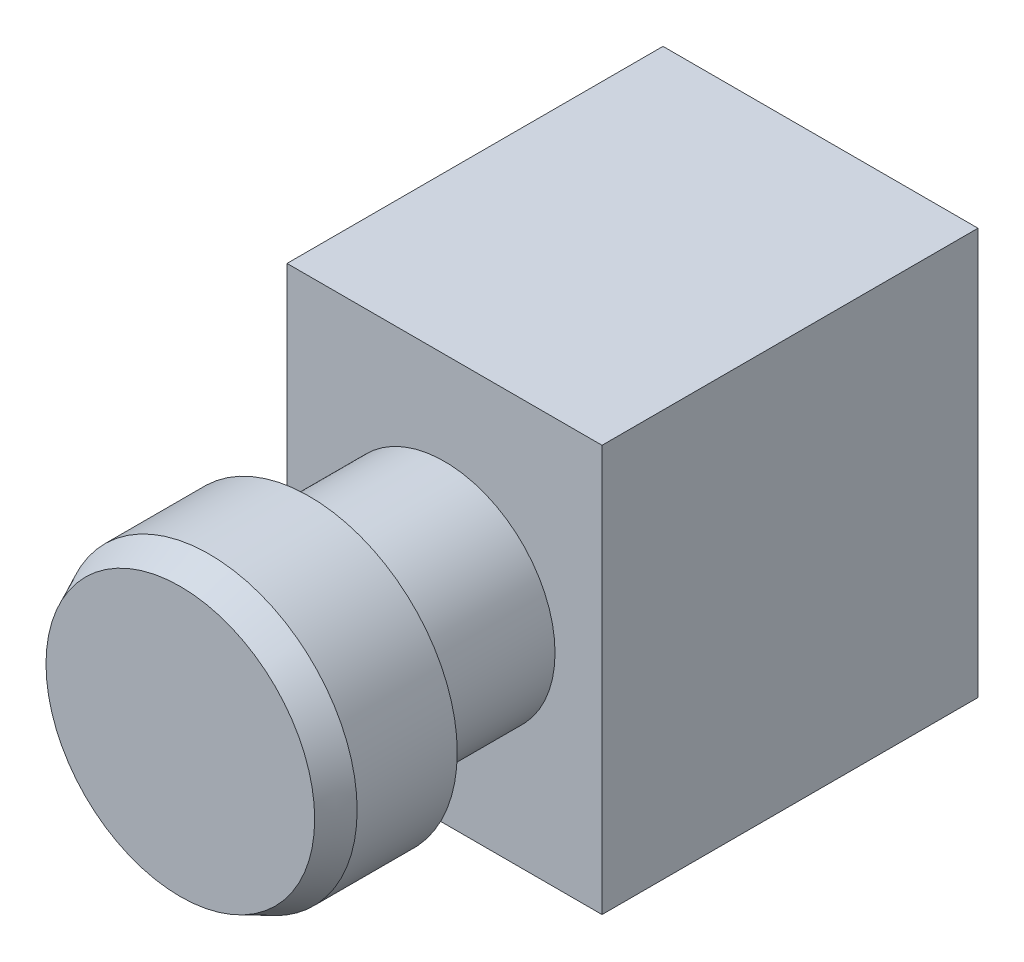
SolidWorks part; units mm, degrees
ref_plane "Front" through (0, 0, 0) normal (0, 0, 1) x (1, 0, 0)
ref_plane "Top" through (0, 0, 0) normal (0, 1, 0) x (1, 0, 0)
ref_plane "Right" through (0, 0, 0) normal (1, 0, 0) x (0, 0, -1)
sketch "Sketch1" plane through (0, 0, 0) normal (0, 0, 1) x (1, 0, 0)
  circle A0 centre (0, 0) radius 14.55
  dimension "D1" = 29.1
extrude "Boss-Extrude1" add sketch "Sketch1" along normal blind 9.85
sketch "Sketch3" plane through (0, 0, 9.85) normal (0, 0, 1) x (1, 0, 0)
  circle A1 centre (0, 0) radius 14.55
  circle A2 centre (0, 0) radius 14.55
  dimension "D1" = 0
extrude "Boss-Extrude3" add sketch "Sketch3" along normal blind 2.85 draft 25
sketch "Sketch4" plane through (0, 0, 0) normal (0, 0, 1) x (1, 0, 0)
  circle A0 centre (0, 0) radius 10.875
  point P2 (0, 0)
  dimension "D1" = 21.75
extrude "Boss-Extrude4" add sketch "Sketch4" against normal blind 13.3
sketch "Sketch2" plane through (0, 0, -13.3) normal (0, 0, 1) x (1, 0, 0)
  line L1 (-15.5, -20) -> (15.5, -20)
  line L2 (-15.5, -20) -> (-15.5, 20)
  line L3 (-15.5, 20) -> (15.5, 20)
  line L4 (15.5, -20) -> (15.5, 20)
  line L5 (-15.5, -20) -> (15.5, 20) construction
  line L6 (-15.5, 20) -> (15.5, -20) construction
  point P0 (0, 0)
  dimension "D1" = 31
  dimension "D2" = 40
extrude "Boss-Extrude2" add sketch "Sketch2" against normal blind 37
sketch "Panel Cut Guide" plane through (0, 0, 0) normal (0, 0, 1) x (1, 0, 0)
  line L0 (-10.15, 3.9733) -> (-10.15, -3.9733)
  line L1 (10.15, 3.9733) -> (10.15, -3.9733)
  line L2 (0, 10.9) -> (0, 0) construction
  circle A0 centre (0, 0) radius 10.9 construction
  arc A1 (-10.15, 3.9733) -> (10.15, 3.9733) centre (0, 0) cw
  arc A2 (10.15, -3.9733) -> (-10.15, -3.9733) centre (0, 0) cw
  point P9 (-10.1185, -4.0529)
  point P10 (10.15, 3.9058)
  dimension "D1" = 21.8
  dimension "D2" = 20.3
